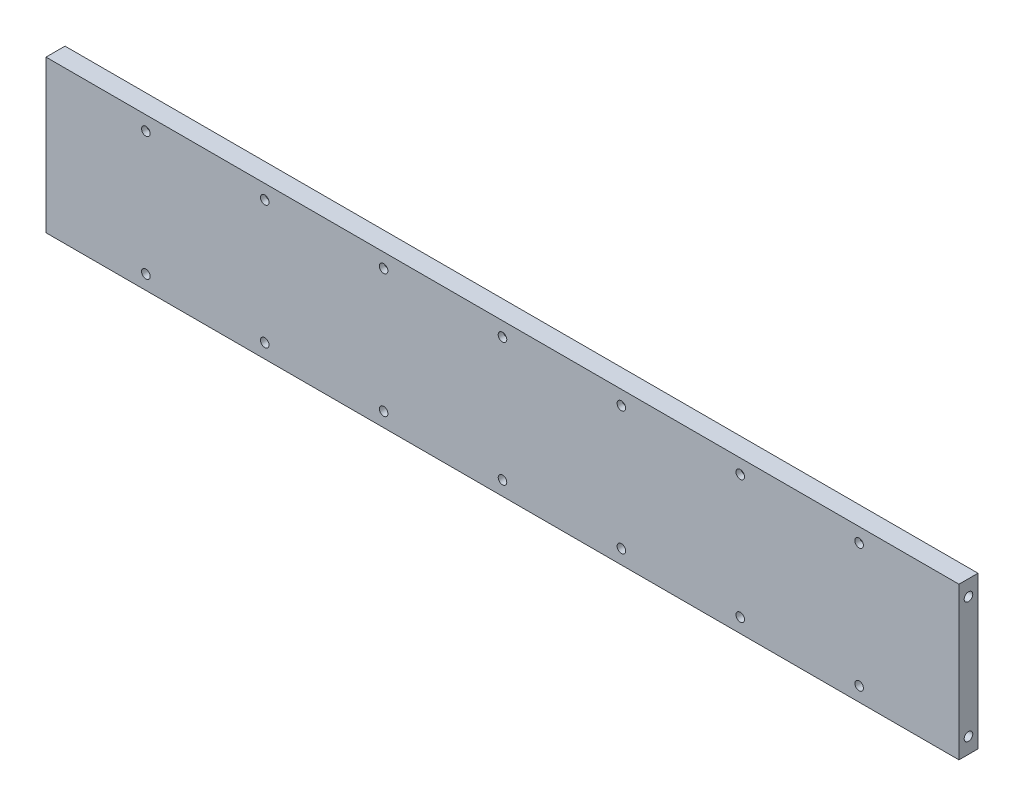
SolidWorks part; units mm, degrees
ref_plane "Front Plane" through (0, 0, 0) normal (0, 0, 1) x (1, 0, 0)
ref_plane "Top Plane" through (0, 0, 0) normal (0, 1, 0) x (1, 0, 0)
ref_plane "Right Plane" through (0, 0, 0) normal (1, 0, 0) x (0, 0, -1)
sketch "Sketch1" plane through (0, 0, 0) normal (0, 0, 1) x (1, 0, 0)
  line L0 (0, 26) -> (0, -26) construction
  line L1 (192, 32) -> (-192, 32)
  line L2 (192, 32) -> (192, -32)
  line L3 (192, -32) -> (-192, -32)
  line L4 (-192, 32) -> (-192, -32)
  line L5 (192, 32) -> (-192, -32) construction
  line L6 (192, -32) -> (-192, 32) construction
  point P0 (0, 0)
  point P8 (0, 0)
  circle B0 centre (0, 26) radius 1.8
  circle B1 centre (50, 26) radius 1.8
  circle B2 centre (100, 26) radius 1.8
  circle B3 centre (150, 26) radius 1.8
  circle B4 centre (-50, 26) radius 1.8
  circle B5 centre (-100, 26) radius 1.8
  circle B6 centre (-150, 26) radius 1.8
  circle B7 centre (-150, -26) radius 1.8
  circle B8 centre (-100, -26) radius 1.8
  circle B9 centre (-50, -26) radius 1.8
  circle B10 centre (150, -26) radius 1.8
  circle B11 centre (100, -26) radius 1.8
  circle B12 centre (50, -26) radius 1.8
  circle B13 centre (0, -26) radius 1.8
  dimension "D1" = 384
  dimension "D2" = 64
sketch_block_instance "Block2-1"
sketch_block "Block2"
extrude "Boss-Extrude1" add sketch "Sketch1" along normal blind 8
sketch "Sketch2" plane through (-192, 0, 0) normal (-1, 0, 0) x (0, 0, 1)
  line L0 (0, 0) -> (8, 0) construction
  line L1 (8, 32) -> (8, -32) construction
  line L2 (4, 32) -> (4, -32) construction
  line L3 (8, 32) -> (0, 32) construction
  line L4 (8, -32) -> (0, -32) construction
  circle A0 centre (4, 25.445) radius 1.8
  circle A1 centre (4, -25.445) radius 1.8
  dimension "D1" = 25.445
extrude "Cut-Extrude1" cut sketch "Sketch2" against normal up to next
